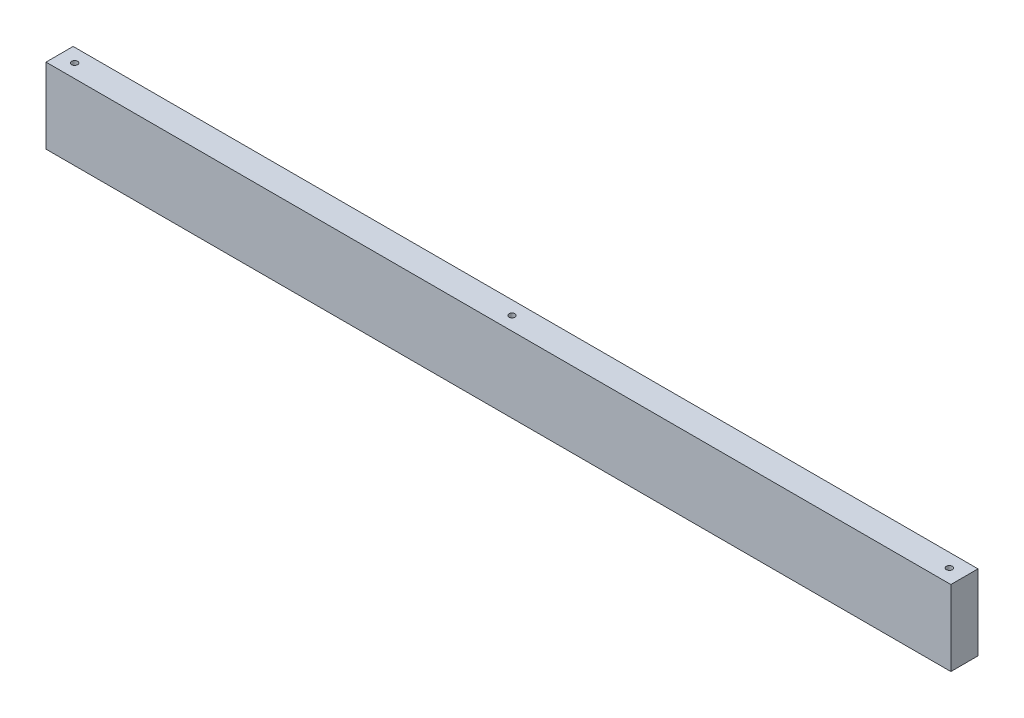
SolidWorks part; units mm, degrees
material "Mahogany"
ref_plane "Front Plane" through (0, 0, 0) normal (0, 0, 1) x (1, 0, 0)
ref_plane "Top Plane" through (0, 0, 0) normal (0, 1, 0) x (1, 0, 0)
ref_plane "Right Plane" through (0, 0, 0) normal (1, 0, 0) x (0, 0, -1)
sketch "Sketch1" plane through (0, 0, 0) normal (0, 0, 1) x (1, 0, 0)
  line L1 (-300, -25) -> (300, -25)
  line L2 (-300, -25) -> (-300, 25)
  line L3 (-300, 25) -> (300, 25)
  line L4 (300, -25) -> (300, 25)
  line L5 (-300, -25) -> (300, 25) construction
  line L6 (-300, 25) -> (300, -25) construction
  point P0 (0, 0)
  dimension "D1" = 600
  dimension "D2" = 50
extrude "Boss-Extrude1" add sketch "Sketch1" along normal blind 18
sketch "Sketch2" plane through (0, 25, 0) normal (0, 1, 0) x (1, 0, 0)
  line L0 (300, -18) -> (300, 0) construction
  line L1 (300, 0) -> (-300, 0) construction
  line L2 (300, -18) -> (-300, -18) construction
  line L3 (-300, -18) -> (-300, 0) construction
  circle A0 centre (-290, -9) radius 2
  circle A1 centre (0, -9) radius 2
  circle A2 centre (290, -9) radius 2
  point P10 (0, 0)
  dimension "D4" = 9
  dimension "D6" = 4
  dimension "D7" = 4
  dimension "D8" = 4
  dimension "D1" = 10
  dimension "D2" = 9
  dimension "D3" = 9
  dimension "D5" = 10
extrude "Cut-Extrude1" cut sketch "Sketch2" against normal blind 25
